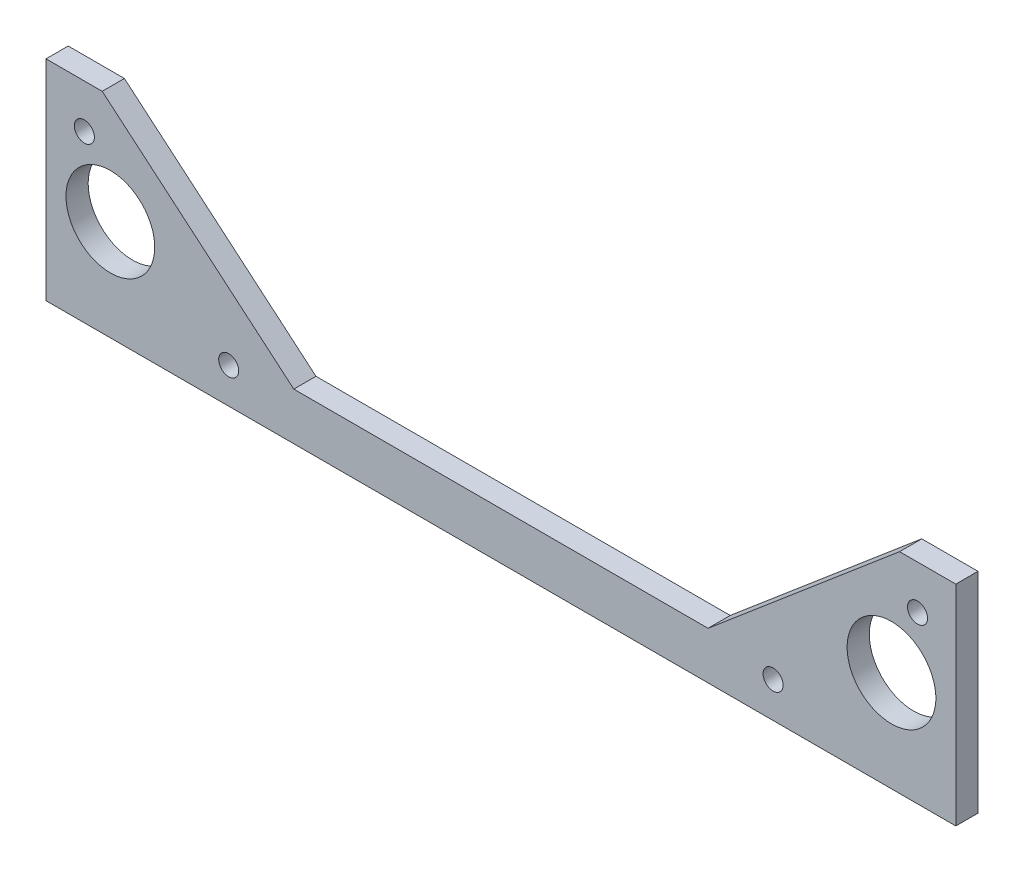
SolidWorks part; units mm, degrees
material "Nylon 101"
ref_plane "Front Plane" through (0, 0, 0) normal (0, 0, 1) x (1, 0, 0)
ref_plane "Top Plane" through (0, 0, 0) normal (0, 1, 0) x (1, 0, 0)
ref_plane "Right Plane" through (0, 0, 0) normal (1, 0, 0) x (0, 0, -1)
sketch "Sketch1" plane through (0, 0, 0) normal (0, 0, 1) x (1, 0, 0)
  line L8 (-44.45, 10.16) -> (-85.5663, 44.958)
  line L9 (-85.5663, 44.958) -> (-97.6313, 44.958)
  line L10 (-97.6313, 44.958) -> (-97.6313, 0)
  line L11 (-97.6313, 0) -> (97.6312, 0)
  line L12 (97.6312, 0) -> (97.6312, 44.958)
  line L13 (97.6312, 44.958) -> (85.5662, 44.958)
  line L14 (85.5662, 44.958) -> (44.45, 10.16)
  line L15 (44.45, 10.16) -> (-44.45, 10.16)
  line L16 (-44.45, 10.16) -> (-85.5663, 44.958)
  line L17 (-85.5663, 44.958) -> (-97.6313, 44.958)
  line L18 (-97.6313, 44.958) -> (-97.6313, 0)
  line L19 (-97.6313, 0) -> (97.6312, 0)
  line L20 (97.6312, 0) -> (97.6312, 44.958)
  line L21 (97.6312, 44.958) -> (85.5662, 44.958)
  line L22 (85.5662, 44.958) -> (44.45, 10.16)
  line L23 (44.45, 10.16) -> (-44.45, 10.16)
  circle A0 centre (-83.82, 21.59) radius 9.525
  circle A1 centre (83.82, 21.59) radius 9.525
  dimension "D2" = 19.05
  dimension "D1" = 0
extrude "Boss-Extrude1" add sketch "Sketch1" along normal blind 4.7625
hole_wizard "#6 Clearance Hole1" positions "Sketch3" profile "Sketch2" hole size "#6" standard "ANSI Inch" end condition through all
sketch "Sketch3" plane through (0, 0, 4.7625) normal (0, 0, 1) x (1, 0, 0)
  point P0 (89.408, 35.56)
  point P3 (58.42, 7.62)
  point P6 (-58.42, 7.62)
  point P9 (-89.408, 35.56)
sketch "Sketch2" plane through (89.408, 35.56, 4.7625) normal (1, 0, 0) x (0, -1, 0)
  line L0 (0, 0) -> (0, 4.7625)
  line L1 (0, 4.7625) -> (2.1526, 4.7625)
  line L2 (2.1526, 4.7625) -> (2.1526, 0)
  line L5 (2.1526, 0) -> (0, 0)
  line L11 (0, -6.35) -> (0, 107.95) construction
  dimension "Thru Hole Dia." = 4.3053
  dimension "Thru Hole Depth" = 4.7625
